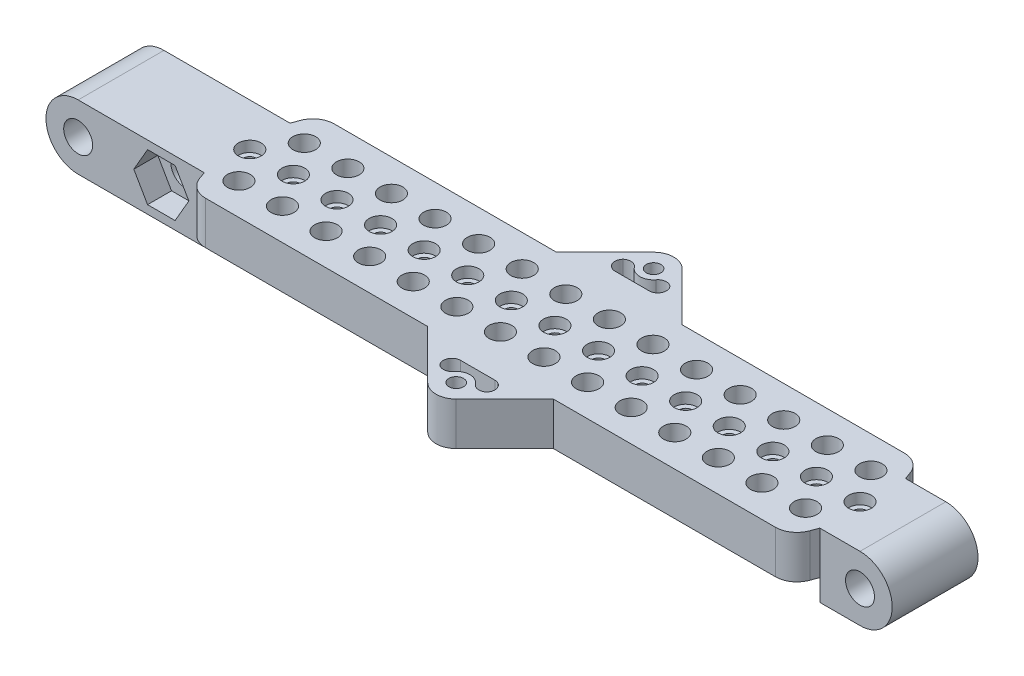
SolidWorks part; units mm, degrees
ref_plane "Front Plane" through (0, 0, 0) normal (0, 0, 1) x (1, 0, 0)
ref_plane "Top Plane" through (0, 0, 0) normal (0, 1, 0) x (1, 0, 0)
ref_plane "Right Plane" through (0, 0, 0) normal (1, 0, 0) x (0, 0, -1)
sketch "Sketch1" plane through (0, 0, 0) normal (0, 1, 0) x (1, 0, 0)
  line L1 (-2.05, 0) -> (2.05, 0) construction
  line L2 (-3.7081, 1.5) -> (3.7081, 1.5) construction
  line L3 (-3.7081, -1.5) -> (3.7081, -1.5) construction
  circle A0 centre (0, 0) radius 4
  circle A1 centre (0, 0) radius 1.5
  circle A2 centre (0, 0) radius 2.5 construction
  point P4 (0, 0)
  point P8 (0, 0)
  point P10 (-2.05, 0)
  dimension "D1" = 8
  dimension "D4" = 5
  dimension "D2" = 4.1
  dimension "D3" = 1.5
extrude "Boss-Extrude1" add sketch "Sketch1" along normal blind 15
sketch "Sketch3" plane through (0, 15, 0) normal (0, 1, 0) x (1, 0, 0)
  circle A0 centre (0, 0) radius 2.65
  dimension "D1" = 5.3
extrude "Cut-Extrude1" cut sketch "Sketch3" against normal blind 2.5
sketch "Sketch2" plane through (0, 15, 0) normal (0, 1, 0) x (1, 0, 0)
  line L0 (0, 4) -> (10.16, 4)
  line L2 (10.16, -4) -> (0, -4)
  line L3 (5.08, 4) -> (5.08, -4) construction
  circle A0 centre (0, 0) radius 4 construction
  arc A1 (0, 4) -> (0, -4) centre (0, 0) cw
  arc A2 (10.16, 4) -> (10.16, -4) centre (10.16, 0) ccw
  dimension "D1" = 10.16
extrude "Boss-Extrude2" add sketch "Sketch2" against normal blind 15
pattern_linear "LPattern2" count 14 spacing 10.16 along (1, 0, 0) of "Boss-Extrude2", "Boss-Extrude1"
pattern_linear "LPattern3" count 2 spacing 142.24 along (1, 0, 0) of "Boss-Extrude1", "Cut-Extrude1"
combine bodies "Combine1" operation type add bodies to combine 114 109 104 117 111 106 113 108 115 110 105 107 112 103
sketch "Sketch4" plane through (0, 15, 0) normal (0, 1, 0) x (1, 0, 0)
  line L0 (0, 0) -> (10.16, 0) construction
  line L1 (5.08, 7.62) -> (5.08, 0) construction
  line L2 (-3.7588, 1.3681) -> (1.2028, 15)
  line L3 (1.2028, 15) -> (141.0372, 15)
  line L4 (0, 0) -> (142.24, 0) construction
  line L5 (71.12, 0) -> (71.12, 15) construction
  line L6 (-3.7588, -1.3681) -> (1.2028, -15)
  line L7 (1.2028, -15) -> (141.0372, -15)
  line L8 (145.9988, 1.3681) -> (141.0372, 15)
  line L9 (145.9988, -1.3681) -> (141.0372, -15)
  line L12 (142.24, 4) -> (0, 4)
  line L13 (0, -4) -> (142.24, -4)
  circle A0 centre (5.08, 7.62) radius 2.65
  circle A1 centre (15.24, 7.62) radius 2.65
  circle A2 centre (25.4, 7.62) radius 2.65
  circle A3 centre (35.56, 7.62) radius 2.65
  circle A4 centre (45.72, 7.62) radius 2.65
  circle A5 centre (55.88, 7.62) radius 2.65
  circle A6 centre (66.04, 7.62) radius 2.65
  circle A7 centre (76.2, 7.62) radius 2.65
  circle A8 centre (86.36, 7.62) radius 2.65
  circle A9 centre (96.52, 7.62) radius 2.65
  circle A10 centre (106.68, 7.62) radius 2.65
  circle A11 centre (116.84, 7.62) radius 2.65
  circle A12 centre (127, 7.62) radius 2.65
  circle A13 centre (137.16, 7.62) radius 2.65
  circle A14 centre (15.24, -7.62) radius 2.65
  circle A15 centre (25.4, -7.62) radius 2.65
  circle A16 centre (35.56, -7.62) radius 2.65
  circle A17 centre (45.72, -7.62) radius 2.65
  circle A18 centre (55.88, -7.62) radius 2.65
  circle A19 centre (66.04, -7.62) radius 2.65
  circle A20 centre (76.2, -7.62) radius 2.65
  circle A21 centre (86.36, -7.62) radius 2.65
  circle A22 centre (96.52, -7.62) radius 2.65
  circle A23 centre (106.68, -7.62) radius 2.65
  circle A24 centre (116.84, -7.62) radius 2.65
  circle A25 centre (127, -7.62) radius 2.65
  circle A26 centre (137.16, -7.62) radius 2.65
  circle A27 centre (5.08, -7.62) radius 2.65
  arc A28 (0, 4) -> (0, -4) centre (0, 0) ccw construction
  circle A29 centre (0, 0) radius 2.65
  circle A30 centre (10.16, 0) radius 2.65 construction
  arc A31 (0, 4) -> (0, -4) centre (0, 0) ccw
  arc A32 (142.24, -4) -> (142.24, 4) centre (142.24, 0) ccw
  arc A33 (-3.7588, 1.3681) -> (-3.7588, -1.3681) centre (0, 0) ccw
  arc A34 (145.9988, -1.3681) -> (145.9988, 1.3681) centre (142.24, 0) ccw
  circle A35 centre (10.16, 0) radius 2.65
  circle A36 centre (20.32, 0) radius 2.65
  circle A37 centre (30.48, 0) radius 2.65
  circle A38 centre (40.64, 0) radius 2.65
  circle A39 centre (50.8, 0) radius 2.65
  circle A40 centre (60.96, 0) radius 2.65
  circle A41 centre (71.12, 0) radius 2.65
  circle A42 centre (81.28, 0) radius 2.65
  circle A43 centre (91.44, 0) radius 2.65
  circle A44 centre (101.6, 0) radius 2.65
  circle A45 centre (111.76, 0) radius 2.65
  circle A46 centre (121.92, 0) radius 2.65
  circle A47 centre (132.08, 0) radius 2.65
  circle A48 centre (142.24, 0) radius 2.65
  circle A49 centre (0, 0) radius 2.65 construction
  point P80 (71.12, -15)
  dimension "D1" = 5.3
  dimension "D11" = 10.16
  dimension "D2" = 7.62
  dimension "D5" = 7.62
  dimension "D6" = 10.16
  dimension "D7" = 15
  dimension "D8" = 20
  dimension "D9" = 0
  dimension "D3" = 14
  dimension "D4" = 2
  dimension "D10" = 15
extrude "Boss-Extrude4" add sketch "Sketch4" against normal blind 10
fillet "Fillet1" radius 5 4 edges at (141.0372, 10, -15) (141.0372, 10, 15) (1.2028, 10, -15) (1.2028, 10, 15)
sketch "Sketch5" plane through (0, 15, 0) normal (0, 1, 0) x (1, 0, 0)
  line L0 (137.5361, 15) -> (4.7039, 15) construction
  line L1 (71.12, 23) -> (71.12, 0) construction
  line L2 (67.7966, 26.3234) -> (56.4732, 15)
  line L3 (56.4732, 15) -> (85.7668, 15)
  line L4 (74.4434, 26.3234) -> (85.7668, 15)
  line L5 (71.12, 0) -> (81.28, 0) construction
  line L6 (74.4434, -26.3234) -> (85.7668, -15)
  line L7 (56.4732, -15) -> (85.7668, -15)
  line L8 (67.7966, -26.3234) -> (56.4732, -15)
  line L10 (62.3016, 18) -> (67.9963, 23.6947)
  line L11 (137.5361, 18) -> (4.7039, 18)
  line L12 (79.9384, 18) -> (62.3016, 18)
  line L13 (79.9384, 18) -> (74.2437, 23.6947)
  line L14 (79.9384, -18) -> (74.2437, -23.6947)
  line L15 (62.3016, -18) -> (67.9963, -23.6947)
  line L16 (79.9384, -18) -> (62.3016, -18)
  circle A0 centre (71.12, 23) radius 1.7
  arc A2 (74.4434, 26.3234) -> (67.7966, 26.3234) centre (71.12, 23) ccw
  arc A3 (74.4434, -26.3234) -> (67.7966, -26.3234) centre (71.12, -23) cw
  circle A4 centre (71.12, -23) radius 1.7
  arc A6 (67.9963, 23.6947) -> (74.2437, 23.6947) centre (71.12, 23) ccw
  arc A7 (67.9963, -23.6947) -> (74.2437, -23.6947) centre (71.12, -23) cw
  point P11 (71.12, 15)
  point P19 (71.12, -15)
  dimension "D1" = 3.4
  dimension "D3" = 3
  dimension "D7" = 1.5
  dimension "D2" = 8
  dimension "D4" = 45
  dimension "D6" = 2
  dimension "D5" = 3
extrude "Boss-Extrude5" add sketch "Sketch5" against normal blind 10
fillet "Fillet2" radius 2 8 edges at (79.9384, 10, -18) (62.3016, 10, -18) (67.9963, 10, -23.6947) (74.2437, 10, -23.6947) (62.3016, 10, 18) (79.9384, 10, 18) (74.2437, 10, 23.6947) (67.9963, 10, 23.6947)
sketch "Sketch6" plane through (0, 15, 0) normal (0, 1, 0) x (1, 0, 0)
  line L0 (-0.617, 10) -> (-30, 10)
  line L1 (0.0054, 11.7101) -> (-3.7588, 1.3681) construction
  line L2 (-30, 10) -> (-30, -10)
  line L3 (0, 0) -> (-30, 0) construction
  line L6 (-0.617, -10) -> (-30, -10)
  line L7 (-0.617, 10) -> (0, 2.65)
  line L8 (-0.617, -10) -> (0, -2.65)
  circle A4 centre (0, 0) radius 2.65 construction
  arc A6 (0, 2.65) -> (0, -2.65) centre (0, 0) ccw
  dimension "D1" = 20
  dimension "D2" = 30
extrude "Boss-Extrude6" add sketch "Sketch6" against normal blind 15
sketch "Sketch10" plane through (0, 0, 10) normal (0, 0, 1) x (1, 0, 0)
  line L0 (-30, 0) -> (-30, 15) construction
  line L1 (-30, 15) -> (-30, 0)
  arc A0 (-30, 15) -> (-30, 0) centre (-30, 7.5) ccw
extrude "Boss-Extrude7" add sketch "Sketch10" against normal up to surface (20 mm away) up to face at (-12.3702, 7, -10)
sketch "Sketch7" plane through (0, 0, 10) normal (0, 0, 1) x (1, 0, 0)
  line L0 (-37.5, 7.5) -> (-0.617, 7.5) construction
  line L2 (-0.617, 5) -> (-0.617, 15) construction
  line L3 (-0.617, 0) -> (-0.617, 5) construction
  line L4 (-7.4091, 1.9437) -> (-4.2012, 7.5)
  line L5 (-4.2012, 7.5) -> (-7.4091, 13.0563)
  line L6 (-7.4091, 13.0563) -> (-13.8249, 13.0563)
  line L7 (-13.8249, 13.0563) -> (-17.0328, 7.5)
  line L8 (-17.0328, 7.5) -> (-13.8249, 1.9437)
  line L9 (-13.8249, 1.9437) -> (-7.4091, 1.9437)
  circle A1 centre (-10.617, 7.5) radius 5.5563 construction
  arc A2 (-30, 15) -> (-30, 0) centre (-30, 7.5) ccw construction
  dimension "D2" = 11.1125
  dimension "D3" = 10
extrude "Cut-Extrude2" cut sketch "Sketch7" against normal blind 5.588
sketch "Sketch8" plane through (0, 0, 10) normal (0, 0, 1) x (1, 0, 0)
  line L0 (-37.5, 7.5) -> (-0.617, 7.5) construction
  line L2 (-0.617, 5) -> (-0.617, 15) construction
  line L3 (-13.8249, 13.0563) -> (-7.4091, 1.9437) construction
  line L4 (-13.8249, 13.0563) -> (-17.0328, 7.5) construction
  circle A0 centre (-10.617, 7.5) radius 3.3734
  circle A1 centre (-30, 7.5) radius 3.3734
  arc A2 (-30, 15) -> (-30, 0) centre (-30, 7.5) ccw construction
  point P13 (-10.617, 7.5)
  dimension "D1" = 6.7469
extrude "Cut-Extrude3" cut sketch "Sketch8" against normal through all
mirror "Mirror2" about plane through (0, 0, 0) normal (0, 0, 1) of "Cut-Extrude2"
sketch "Sketch11" plane through (0, 15, 0) normal (0, 1, 0) x (1, 0, 0)
  line L0 (-0.617, 10) -> (142.857, 10) construction
  line L1 (145.9988, 1.3681) -> (142.2346, 11.7101) construction
  line L2 (0, 0) -> (142.24, 0) construction
  line L3 (142.857, 10) -> (152.24, 10)
  line L4 (152.24, 10) -> (152.24, -10)
  line L5 (142.857, 10) -> (142.24, 2.65)
  line L6 (142.24, -2.65) -> (142.24, 2.65) construction
  line L7 (142.24, 2.65) -> (142.24, -2.65) construction
  line L8 (142.857, -10) -> (142.24, -2.65)
  line L9 (142.857, -10) -> (152.24, -10)
  circle A1 centre (142.24, 0) radius 2.65 construction
  circle A2 centre (142.24, 0) radius 2.65 construction
  arc A3 (142.24, -2.65) -> (142.24, 2.65) centre (142.24, 0) ccw
  circle A4 centre (132.08, 0) radius 2.65 construction
  point P17 (152.24, 0)
  dimension "D1" = 10
extrude "Boss-Extrude8" add sketch "Sketch11" against normal through all
sketch "Sketch12" plane through (0, 0, 10) normal (0, 0, 1) x (1, 0, 0)
  line L0 (152.24, 0) -> (152.24, 15) construction
  line L1 (152.24, 15) -> (152.24, 0)
  arc A0 (152.24, 15) -> (152.24, 0) centre (152.24, 7.5) cw
extrude "Boss-Extrude9" add sketch "Sketch12" against normal up to surface (20 mm away) up to face at (146.6102, 7, -10)
sketch "Sketch13" plane through (0, 0, 10) normal (0, 0, 1) x (1, 0, 0)
  line L0 (159.74, 7.5) -> (155.6134, 7.5) construction
  circle A0 centre (152.24, 7.5) radius 3.3734
  arc A1 (152.24, 0) -> (152.24, 15) centre (152.24, 7.5) ccw construction
  dimension "D1" = 6.7469
extrude "Cut-Extrude4" cut sketch "Sketch13" against normal through all
